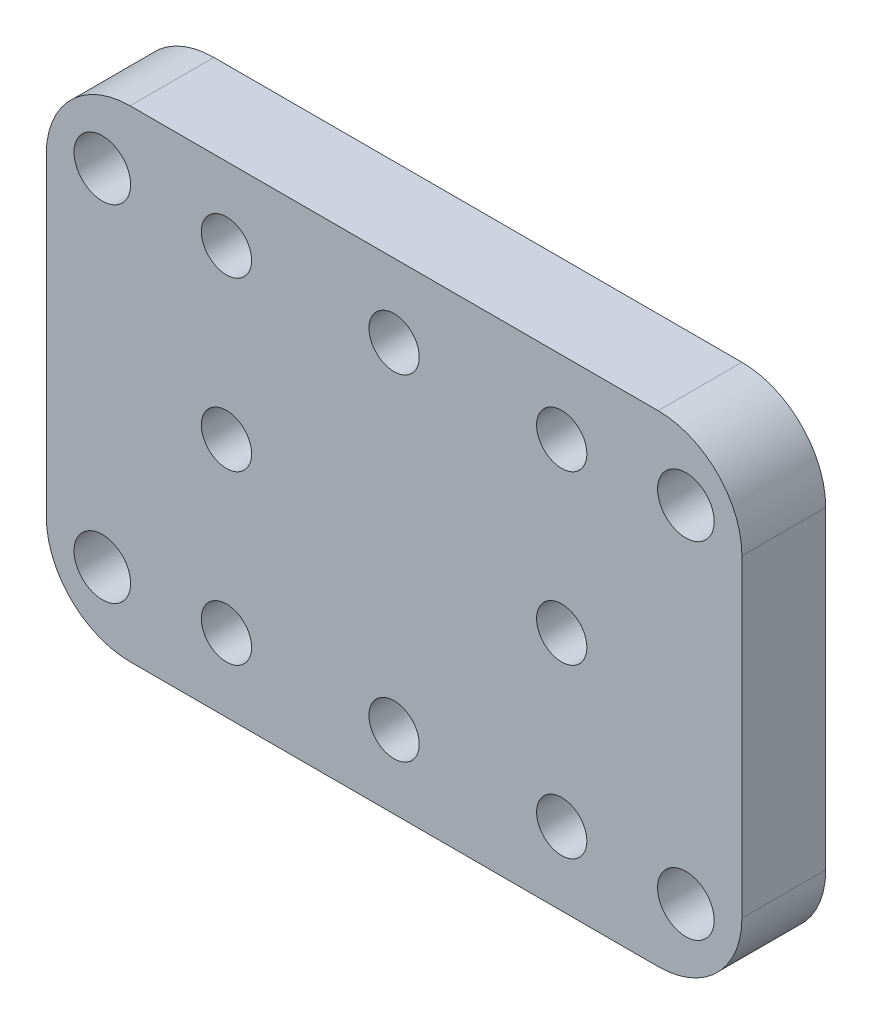
SolidWorks part; units mm, degrees
ref_plane "Alzado" through (0, 0, 0) normal (0, 0, 1) x (1, 0, 0)
ref_plane "Planta" through (0, 0, 0) normal (0, 1, 0) x (1, 0, 0)
ref_plane "Vista lateral" through (0, 0, 0) normal (1, 0, 0) x (0, 0, -1)
sketch "Croquis1" plane through (0, 0, 0) normal (0, 0, 1) x (1, 0, 0)
  line L0 (-0.0106, 23.1539) -> (33.1904, 23.1539)
  line L5 (-0.0106, 23.1539) -> (-0.0106, 0.1756)
  line L6 (-0.0106, 0.1756) -> (33.1904, 0.1756)
  line L7 (33.1904, 23.1539) -> (33.1904, 0.1756)
  circle A0 centre (3.0649, 19.4414) radius 1.3479
  circle A1 centre (30.1148, 19.4414) radius 1.35
  circle A2 centre (30.1148, 3.8881) radius 1.35
  circle A3 centre (3.0649, 3.8881) radius 1.3526
extrude "Saliente-Extruir1" add sketch "Croquis1" along normal blind 4 contours L0 L7 L6 L5
fillet "Redondeo2" radius 4 2 edges at (33.1904, 0.1756, 2) (33.1904, 23.1539, 2)
fillet "Redondeo3" radius 4 2 edges at (-0.0106, 0.1756, 2) (-0.0106, 23.1539, 2)
sketch "Croquis4" plane through (0, 0, 4) normal (0, 0, 1) x (1, 0, 0)
  line L0 (16.5899, 3.6647) -> (16.5899, 0.1756) construction
  line L1 (8.5899, 19.6647) -> (24.5899, 19.6647)
  line L2 (8.5899, 19.6647) -> (8.5899, 3.6647)
  line L3 (8.5899, 3.6647) -> (24.5899, 3.6647)
  line L4 (24.5899, 19.6647) -> (24.5899, 3.6647)
  line L5 (3.9894, 0.1756) -> (29.1904, 0.1756) construction
  line L6 (16.5899, 23.1539) -> (16.5899, 19.6647) construction
  line L7 (24.5899, 11.6647) -> (33.1904, 11.6647) construction
  line L8 (33.1904, 19.1539) -> (33.1904, 4.1756) construction
  line L9 (3.9894, 23.1539) -> (29.1904, 23.1539) construction
  line L10 (8.5899, 11.6647) -> (-0.0106, 11.6647) construction
  line L11 (-0.0106, 19.1539) -> (-0.0106, 4.1756) construction
  circle A0 centre (8.5899, 19.6647) radius 1.2
  circle A1 centre (16.5899, 19.6647) radius 1.2
  circle A2 centre (24.5899, 19.6647) radius 1.2
  circle A3 centre (8.5899, 11.6647) radius 1.2
  circle A4 centre (24.5899, 11.6647) radius 1.2
  circle A5 centre (8.5899, 3.6647) radius 1.2
  circle A6 centre (16.5899, 3.6647) radius 1.2
  circle A7 centre (24.5899, 3.6647) radius 1.2
  dimension "D1" = 16
extrude "Cortar-Extruir3" cut sketch "Croquis4" against normal through all contours L1 A0 L2 | L2 A0 L1 | L2 A3 | L2 A3 | L2 A5 L3 | L3 A5 L2 | L3 A6 | L3 A6 | L3 A7 L4 | L4 A7 L3 | L4 A4 | L4 A4 | L4 A2 L1 | L1 A2 L4 | L1 A1 | L1 A1 region at (8.4201, 19.8345, 4) region at (9.0992, 19.1554, 4) region at (16.5899, 20.174, 4) region at (16.5899, 19.1554, 4) region at (9.0992, 11.6647, 4) region at (8.0806, 11.6647, 4) region at (24.7596, 19.8345, 4) region at (24.0806, 19.1554, 4) region at (9.0992, 4.174, 4) region at (8.4201, 3.495, 4) region at (25.0992, 11.6647, 4) region at (24.0806, 11.6647, 4) region at (16.5899, 4.174, 4) region at (16.5899, 3.1554, 4) region at (24.7596, 3.495, 4) region at (24.0806, 4.174, 4)
sketch3d "Croquis3D2"
  circle A1 centre (2.6649, 3.4247, 13) radius 1.35
  circle A2 centre (2.6649, 3.4247, 13) radius 1.35
  circle A3 centre (2.6649, 19.9047, 13) radius 1.35
  circle A4 centre (2.6649, 19.9047, 13) radius 1.35
  circle A5 centre (30.5149, 3.4247, 13) radius 1.35
  circle A6 centre (30.5149, 3.4247, 13) radius 1.35
  circle A7 centre (30.5149, 19.9047, 13) radius 1.35
  circle A8 centre (30.5149, 19.9047, 13) radius 1.35
  point P5 (2.6649, 3.4247, 14.35)
  point P7 (2.6649, 3.4247, 14.35)
  point P10 (2.6649, 19.9047, 14.35)
  point P12 (2.6649, 19.9047, 14.35)
  point P15 (30.5149, 3.4247, 14.35)
  point P17 (30.5149, 3.4247, 14.35)
  point P20 (30.5149, 19.9047, 14.35)
  point P22 (30.5149, 19.9047, 14.35)
  dimension "D1" = 0
  dimension "D2" = 0
  dimension "D3" = 0
  dimension "D4" = 0
extrude "Cortar-Extruir4" cut sketch "Croquis3D2" along direction (0, 0, 1) on the side against the normal blind 23
sketch "Croquis5" plane through (0, 0, 0) normal (0, 0, -1) x (-1, 0, 0)
  circle A0 centre (-30.5149, 19.9047) radius 2
  circle A1 centre (-2.6649, 19.9047) radius 2
  circle A2 centre (-30.5149, 3.4247) radius 2
  circle A3 centre (-2.6649, 3.4247) radius 2
extrude "Cortar-Extruir5" cut sketch "Croquis5" against normal blind 2
